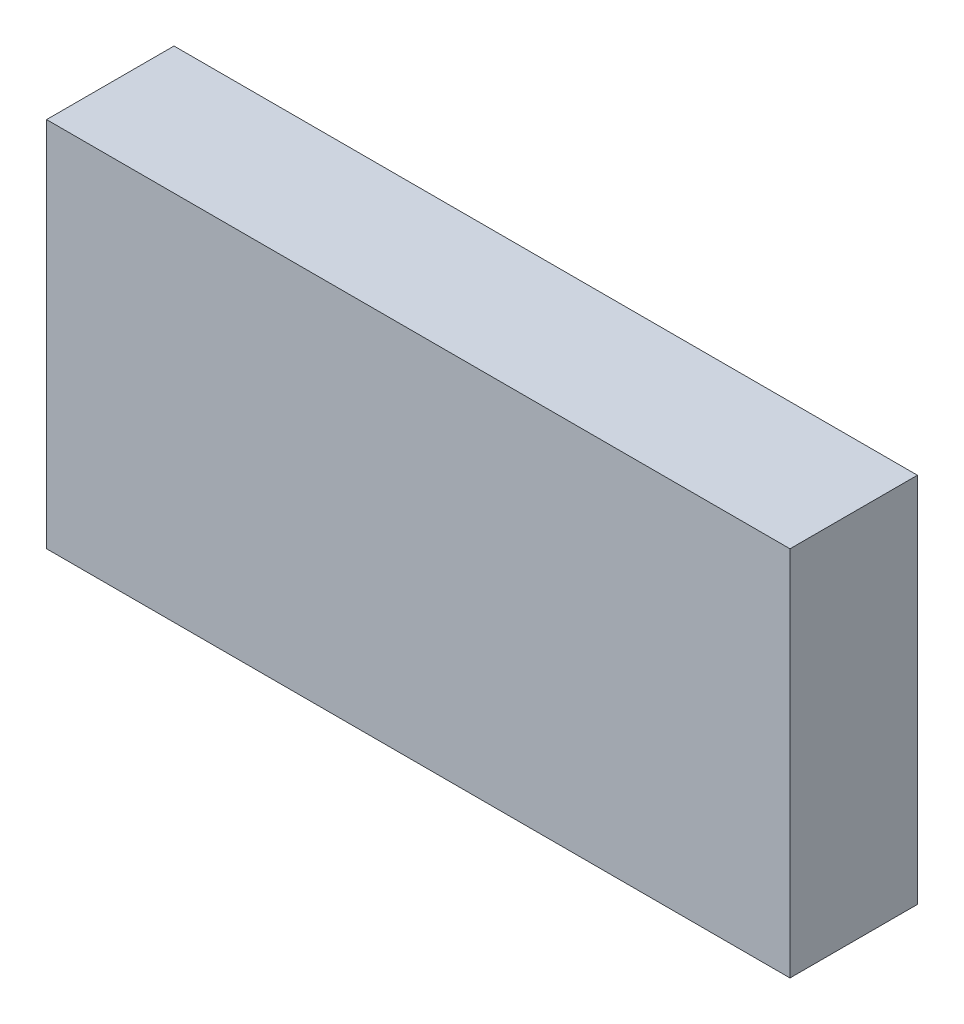
SolidWorks part; units mm, degrees
ref_plane "Front Plane" through (0, 0, 0) normal (0, 0, 1) x (1, 0, 0)
ref_plane "Top Plane" through (0, 0, 0) normal (0, 1, 0) x (1, 0, 0)
ref_plane "Right Plane" through (0, 0, 0) normal (1, 0, 0) x (0, 0, -1)
sketch "Sketch1" plane through (0, 0, 0) normal (0, 0, 1) x (1, 0, 0)
  line L1 (-35, -17.5) -> (35, -17.5)
  line L2 (-35, -17.5) -> (-35, 17.5)
  line L3 (-35, 17.5) -> (35, 17.5)
  line L4 (35, -17.5) -> (35, 17.5)
  line L5 (-35, -17.5) -> (35, 17.5) construction
  line L6 (-35, 17.5) -> (35, -17.5) construction
  point P0 (0, 0)
  dimension "D1" = 70
  dimension "D2" = 35
extrude "Boss-Extrude1" add sketch "Sketch1" along normal mid plane 12
